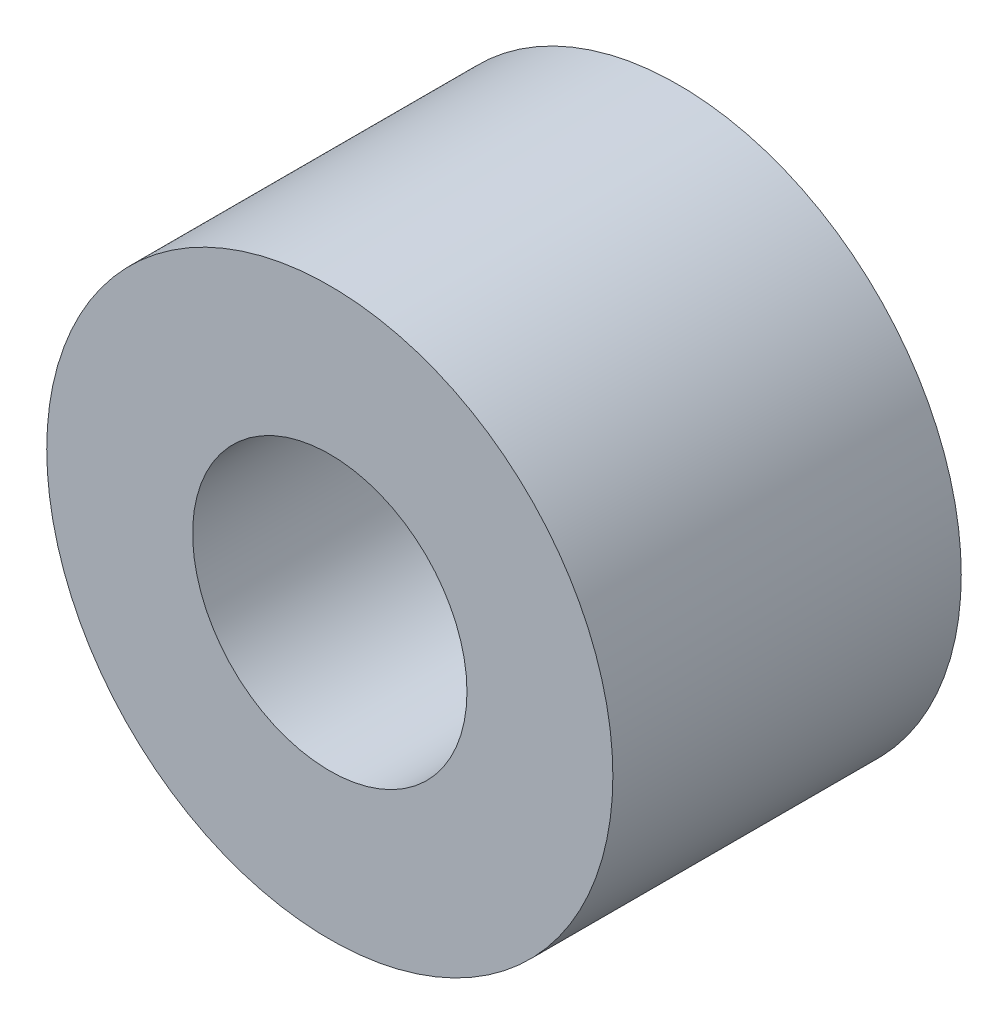
SolidWorks part; units mm, degrees
material "Nylon-6/10"
ref_plane "Front Plane" through (0, 0, 0) normal (0, 0, 1) x (1, 0, 0)
ref_plane "Top Plane" through (0, 0, 0) normal (0, 1, 0) x (1, 0, 0)
ref_plane "Right Plane" through (0, 0, 0) normal (1, 0, 0) x (0, 0, -1)
sketch "Sketch1" plane through (0, 0, 0) normal (0, 0, 1) x (1, 0, 0)
  circle A0 centre (0, 0) radius 6.5
  circle A1 centre (0, 0) radius 3.15
  dimension "OD" = 13
  dimension "ID" = 6.3
extrude "Extrude1" add sketch "Sketch1" along normal mid plane 8
sketch "Sketch2" plane through (0, 0, 0) normal (1, 0, 0) x (0, 0, -1)
  line L0 (-4, -3.15) -> (4, -3.15) construction
  line L3 (4, 3.15) -> (-4, 3.15) construction
  line L5 (-4, -3.15) -> (4, -3.15)
  line L6 (4, 3.15) -> (-4, 3.15)
sketch "Sketch4" plane through (0, 0, 4) normal (0, 0, 1) x (1, 0, 0)
  line L0 (0, 0) -> (-2.2274, 2.2274)
  line L1 (0, -7.15) -> (0, 7.15) construction
  circle A0 centre (0, 0) radius 3.15 construction
  dimension "D1" = 45
